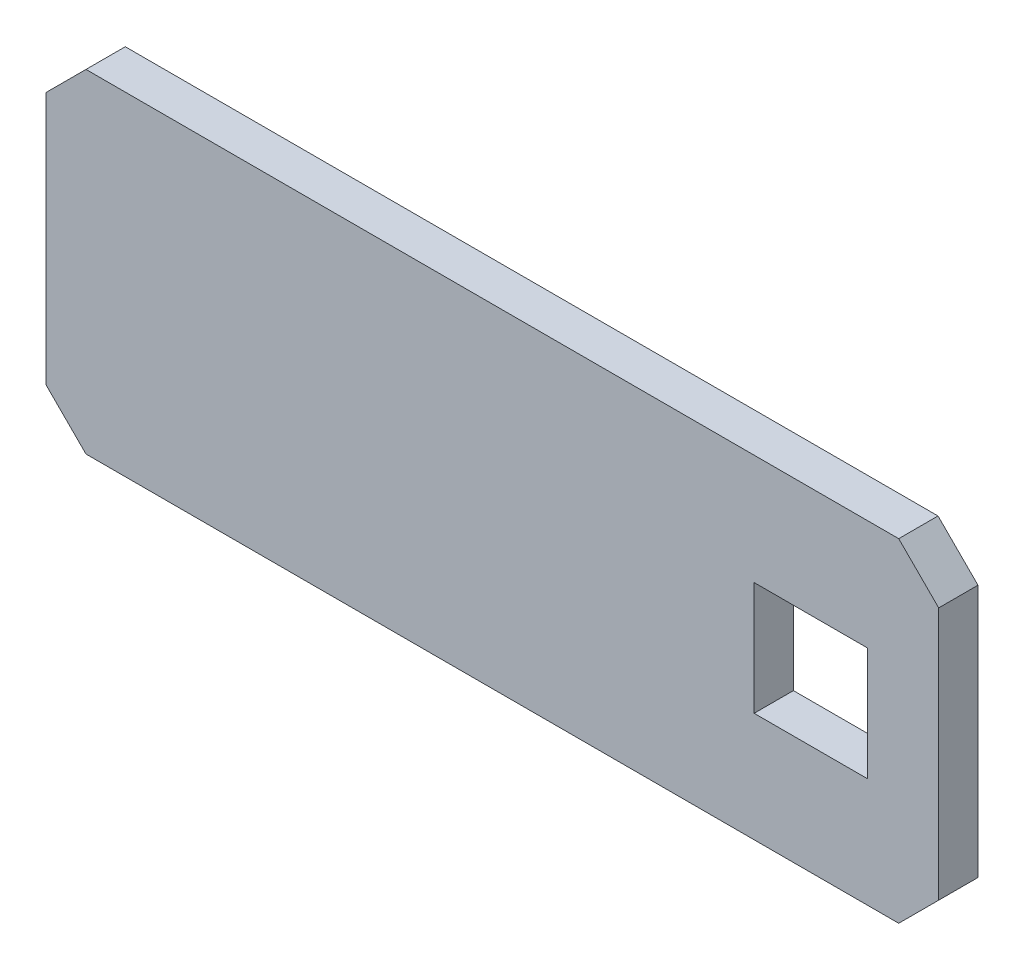
SolidWorks part; units mm, degrees
ref_plane "Спереди" through (0, 0, 0) normal (0, 0, 1) x (1, 0, 0)
ref_plane "Сверху" through (0, 0, 0) normal (0, 1, 0) x (1, 0, 0)
ref_plane "Справа" through (0, 0, 0) normal (1, 0, 0) x (0, 0, -1)
sketch "Эскиз1" plane through (0, 0, 0) normal (0, 0, 1) x (1, 0, 0)
  line L1 (-64.3457, 31.0161) -> (19.6543, 31.0161)
  line L2 (-64.3457, 31.0161) -> (-64.3457, -23.9839)
  line L3 (-64.3457, -23.9839) -> (19.6543, -23.9839)
  line L4 (19.6543, 31.0161) -> (19.6543, -23.9839)
  dimension "D1" = 84
  dimension "D2" = 55
sheet metal parameters "Листовой металл1" thickness 2.95 parameters "D1"=0.7366
base flange "Базовая кромка1" sketch "Эскиз1" thickness 2.95 reverse thickness direction no parameters "D1"=0.7366
sketch "Эскиз5" plane through (0, 0, -2.95) normal (0, 0, -1) x (-1, 0, 0)
  line L0 (64.3457, -8.4839) -> (-2.6543, -8.4839)
  line L1 (64.3457, 31.0161) -> (64.3457, -23.9839) construction
  line L2 (64.3457, -23.9839) -> (-19.6543, -23.9839) construction
  line L3 (64.3457, 16.5161) -> (-2.6543, 16.5161)
  line L4 (-2.6543, 16.5161) -> (-2.6543, -8.4839)
  line L10 (2.6982, -0.262) -> (11.1982, -0.262)
  line L11 (2.6982, -0.262) -> (2.6982, 8.238)
  line L12 (2.6982, 8.238) -> (11.1982, 8.238)
  line L17 (64.3457, 16.5161) -> (64.3457, -8.4839)
  line L21 (11.1982, -0.262) -> (11.1982, 8.238)
  line L22 (2.6982, -0.262) -> (11.1982, 8.238) construction
  line L23 (2.6982, 8.238) -> (11.1982, -0.262) construction
  circle A4 centre (6.9482, 3.988) radius 4.25 construction
  dimension "D8" = 12.4719
  dimension "D17" = 8.5
  dimension "D1" = 15.5
  dimension "D2" = 25
  dimension "D3" = 67
  dimension "D10" = 57.3975
extrude "Вырез-Вытянуть1" cut sketch "Эскиз5" against normal blind 10
chamfer "Фаска1" distance 3 angle 45 4 edges at (2.6543, 16.5161, -1.475) (2.6543, -8.4839, -1.475) (-64.3457, -8.4839, -1.475) (-64.3457, 16.5161, -1.475)
flat pattern "Развертка1" [suppressed]
sketch "Сгиб-Линии1" plane through (0, 0, 0) normal (0, 1, 0) x (-1, 0, 0)
sketch3d "Граничная рамка1" [suppressed]
  line L0 (-4.4206, 62.0379, 0) -> (-91.6389, 44.1366, 0) construction
  line L1 (4.9238, 16.5106, 0) -> (-82.2945, -1.3908, 0) construction
  line L2 (-4.4206, 62.0379, 0) -> (4.9238, 16.5106, 0) construction
  line L3 (-91.6389, 44.1366, 0) -> (-82.2945, -1.3908, 0) construction
